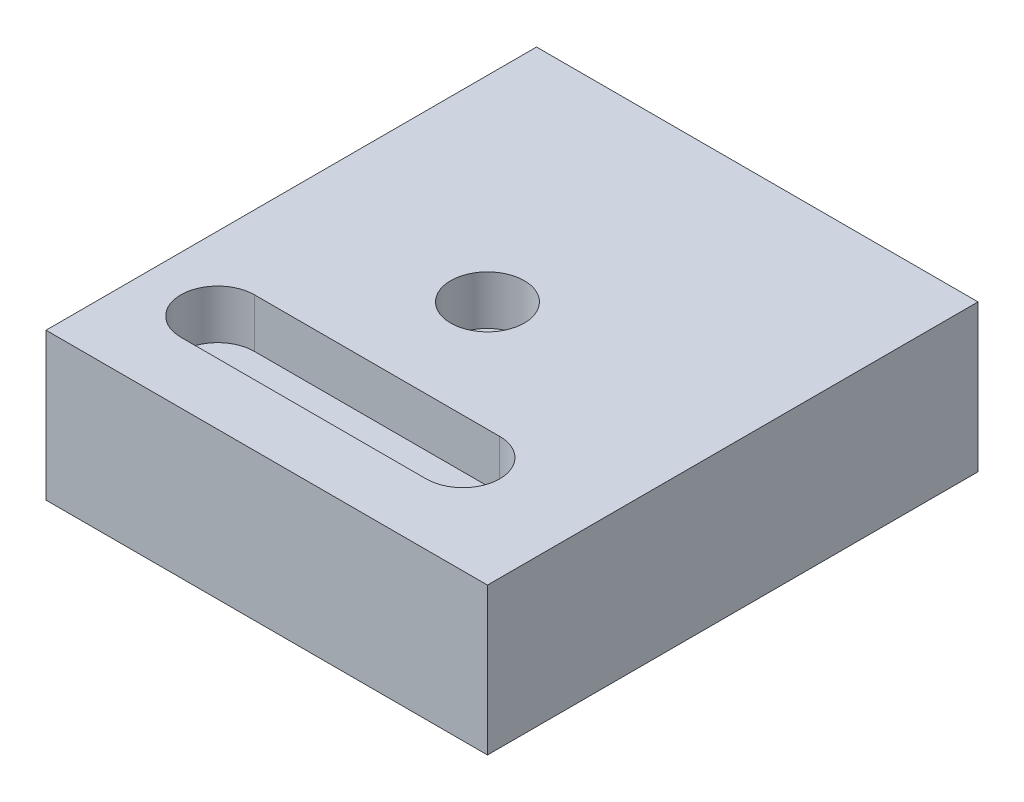
SolidWorks part; units mm, degrees
ref_plane "前视基准面" through (0, 0, 0) normal (0, 0, 1) x (1, 0, 0)
ref_plane "上视基准面" through (0, 0, 0) normal (0, 1, 0) x (1, 0, 0)
ref_plane "右视基准面" through (0, 0, 0) normal (1, 0, 0) x (0, 0, -1)
other "Configuration Table"
sketch "草图1" plane through (0, 0, 0) normal (0, 1, 0) x (1, 0, 0)
  line L0 (80, -50) -> (180, -50)
  line L1 (-50, -50) -> (50, -50)
  line L2 (-50, -50) -> (-50, 50)
  line L3 (-50, 50) -> (50, 50)
  line L4 (50, -50) -> (50, 50)
  line L5 (0, 50) -> (0, -50) construction
  line L6 (-50, 0) -> (50, 0) construction
  line L7 (180, -50) -> (80, 50)
  line L8 (80, 50) -> (80, -50)
  point P0 (0, 0)
  dimension "D1" = 100
  dimension "D2" = 30
extrude "凸台-拉伸1" add sketch "草图1" along normal blind 30
ref_axis "基准轴1" through (0, 0, 0) along (0, 1, 0)
mirror "镜向3" about plane through (0, 0, 0) normal (1, 0, 0) of bodies 107
sketch "草图2" plane through (0, 30, 0) normal (0, 1, 0) x (1, 0, 0)
  line L0 (-25, -30) -> (25, -30) construction
  line L1 (-25, -22.5) -> (25, -22.5)
  line L2 (-25, -37.5) -> (25, -37.5)
  line L3 (0, -30) -> (0, 0) construction
  circle A0 centre (0, 0) radius 7.5
  arc A1 (-25, -22.5) -> (-25, -37.5) centre (-25, -30) ccw
  arc A2 (25, -37.5) -> (25, -22.5) centre (25, -30) ccw
  point P5 (0, -30)
  dimension "D1" = 15
  dimension "D2" = 7.5
  dimension "D3" = 50
  dimension "D4" = 30
extrude "切除-拉伸2" cut sketch "草图2" against normal blind 10
sketch "草图3" plane through (0, 30, 0) normal (0, 1, 0) x (1, 0, 0)
  line L0 (80, 50) -> (80, -50) construction
  line L1 (80, -50) -> (180, -50) construction
  line L2 (180, -50) -> (80, 50) construction
  line L3 (-80, -50) -> (-80, 50) construction
  line L4 (-80, 50) -> (-180, -50) construction
  line L5 (-180, -50) -> (-80, -50) construction
  line L6 (80, 50) -> (80, -50)
  line L7 (80, -50) -> (180, -50)
  line L8 (180, -50) -> (80, 50)
  line L9 (-80, -50) -> (-80, 50)
  line L10 (-80, 50) -> (-180, -50)
  line L11 (-180, -50) -> (-80, -50)
extrude "切除-拉伸3" cut sketch "草图3" against normal through all both and the other way through all
sketch "草图5" plane through (-50, 0, 0) normal (-1, 0, 0) x (0, 0, 1)
  line L4 (-50, 0) -> (50, 0)
  line L5 (50, 0) -> (50, 30)
  line L6 (50, 30) -> (-50, 30)
  line L7 (-50, 30) -> (-50, 0)
  line L8 (-50, 0) -> (50, 0)
  line L9 (50, 0) -> (50, 30)
  line L10 (50, 30) -> (-50, 30)
  line L11 (-50, 30) -> (-50, 0)
  dimension "D1" = 0
extrude "切除-拉伸4" cut sketch "草图5" against normal blind 10 and the other way through all
